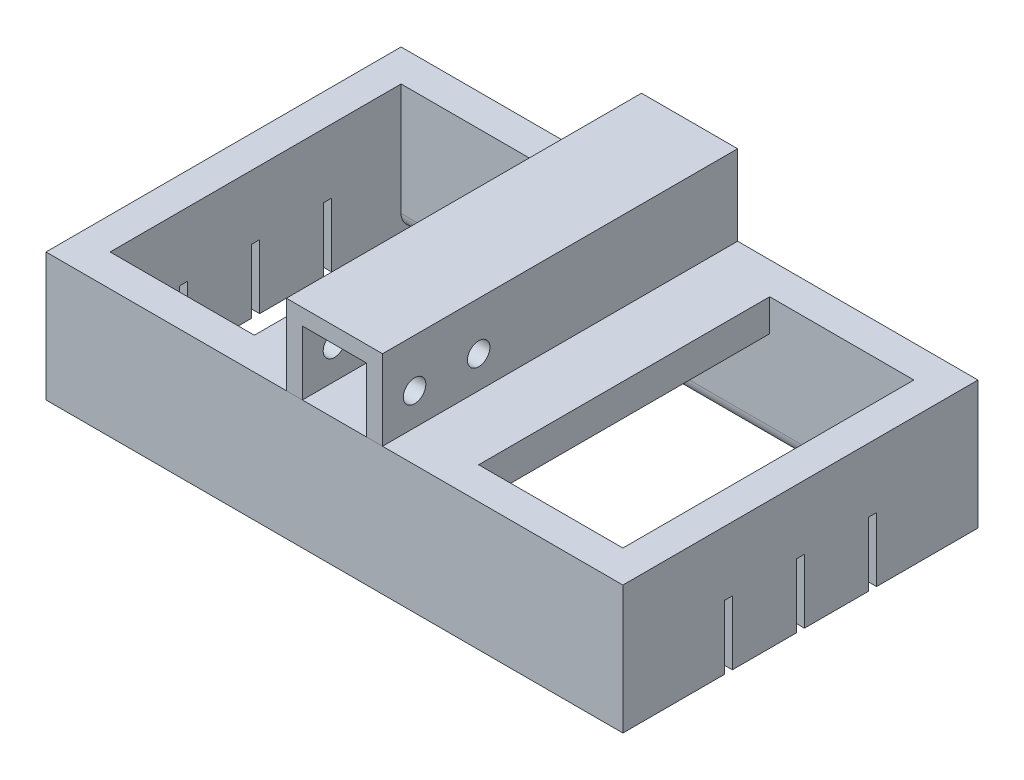
SolidWorks part; units mm, degrees
ref_plane "Front Plane" through (0, 0, 0) normal (0, 0, 1) x (1, 0, 0)
ref_plane "Top Plane" through (0, 0, 0) normal (0, 1, 0) x (1, 0, 0)
ref_plane "Right Plane" through (0, 0, 0) normal (1, 0, 0) x (0, 0, -1)
sketch "Sketch2" plane through (0, 0, 0) normal (0, 1, 0) x (1, 0, 0)
  line L0 (-57.15, -35.179) -> (-57.15, 35.179)
  line L1 (-50.8, -28.829) -> (50.8, -28.829)
  line L2 (-50.8, -28.829) -> (-50.8, 28.829)
  line L3 (-50.8, 28.829) -> (50.8, 28.829)
  line L4 (50.8, -28.829) -> (50.8, 28.829)
  line L5 (-50.8, -28.829) -> (50.8, 28.829) construction
  line L6 (-50.8, 28.829) -> (50.8, -28.829) construction
  line L7 (-57.15, 35.179) -> (57.15, 35.179)
  line L8 (57.15, -35.179) -> (57.15, 35.179)
  line L9 (-57.15, -35.179) -> (57.15, -35.179)
  point P0 (0, 0)
  point P10 (57.15, 35.179)
  dimension "D1" = 57.658
  dimension "D2" = 101.6
  dimension "D3" = 6.35
sketch "Sketch3" plane through (0, 0, 0) normal (0, 0, 1) x (1, 0, 0)
  line L0 (0, 0) -> (0, 12.7) construction
  line L1 (-50.8, 0) -> (50.8, 0) construction
  line L2 (0, 12.7) -> (0, 19.05) construction
  point P6 (0, 0)
  point P8 (0, 0)
  point P11 (0, 0)
  dimension "D1" = 12.7
  dimension "D2" = 6.35
sketch "Sketch4" plane through (0, 0, 0) normal (0, 1, 0) x (1, 0, 0)
  line L4 (-50.8, -28.829) -> (50.8, -28.829)
  line L5 (50.8, -28.829) -> (50.8, 28.829)
  line L6 (50.8, 28.829) -> (-50.8, 28.829)
  line L7 (-50.8, 28.829) -> (-50.8, -28.829)
  line L8 (-50.8, -28.829) -> (50.8, -28.829)
  line L9 (50.8, -28.829) -> (50.8, 28.829)
  line L10 (50.8, 28.829) -> (-50.8, 28.829)
  line L11 (-50.8, 28.829) -> (-50.8, -28.829)
  line L12 (-57.15, 35.179) -> (-57.15, -35.179)
  line L13 (57.15, 35.179) -> (-57.15, 35.179)
  line L14 (57.15, -35.179) -> (57.15, 35.179)
  line L15 (-57.15, -35.179) -> (57.15, -35.179)
  line L16 (-57.15, 35.179) -> (-57.15, -35.179)
  line L17 (57.15, 35.179) -> (-57.15, 35.179)
  line L18 (57.15, -35.179) -> (57.15, 35.179)
  line L19 (-57.15, -35.179) -> (57.15, -35.179)
  dimension "D1" = 0
  dimension "D2" = 0
extrude "Boss-Extrude1" add sketch "Sketch4" along normal up to vertex (19.05 mm away) up to point (0, 19.05, 0)
sketch "Sketch5" plane through (0, 0, 0) normal (0, 1, 0) x (1, 0, 0)
  line L0 (-57.15, -35.179) -> (57.15, -35.179) construction
  line L1 (57.15, -35.179) -> (57.15, 35.179) construction
  line L2 (-57.15, 35.179) -> (57.15, 35.179) construction
  line L3 (-57.15, -35.179) -> (-57.15, 35.179) construction
  line L4 (-57.15, -35.179) -> (57.15, -35.179)
  line L5 (57.15, -35.179) -> (57.15, 35.179)
  line L6 (-57.15, 35.179) -> (57.15, 35.179)
  line L7 (-57.15, -35.179) -> (-57.15, 35.179)
extrude "Boss-Extrude2" add sketch "Sketch5" along normal blind 6.35 from surface contours L4 L5 L6 L7 starting at face at (0, 19.05, 0)
sketch "Sketch6" plane through (-57.15, 0, 0) normal (-1, 0, 0) x (0, 0, 1)
  line L0 (0, 0) -> (0, 12.7)
  line L1 (0, 0) -> (0, 12.7) construction
  line L2 (14.2875, 0) -> (14.2875, 12.7)
  line L3 (35.179, 0) -> (-35.179, 0) construction
  line L4 (-14.2875, 0) -> (-14.2875, 12.7)
  dimension "D1" = 14.2875
  dimension "D2" = 14.2875
extrude "Cut-Extrude-Thin1" cut sketch "Sketch6" against normal through all thin thin type mid plane wall 1.5875
fillet "Fillet1" radius 3.175 2 edges at (0, 0, -28.829) (0, 0, 28.829)
sketch "Sketch8" plane through (0, 0, 35.179) normal (0, 0, 1) x (1, 0, 0)
  line L0 (-9.525, 25.4) -> (-9.525, 41.275)
  line L5 (57.15, 25.4) -> (-57.15, 25.4) construction
  line L6 (-9.525, 41.275) -> (9.525, 41.275)
  line L12 (9.525, 41.275) -> (9.525, 25.4)
  line L13 (9.525, 25.4) -> (6.35, 25.4)
  line L14 (6.35, 25.4) -> (6.35, 38.1)
  line L15 (6.35, 38.1) -> (-6.35, 38.1)
  line L16 (-6.35, 38.1) -> (-6.35, 25.4)
  line L17 (-6.35, 25.4) -> (-9.525, 25.4)
  point P1 (0, 41.275)
  line M7 (57.15, 25.4) -> (-57.15, 25.4)
  dimension "D1" = 12.7
  dimension "D3" = 3.175
  dimension "D2" = 12.7
  dimension "D4" = 3.175
  dimension "D5" = 3.175
extrude "Boss-Extrude3" add sketch "Sketch8" against normal up to surface (70.358 mm away) separate body contours L16 M7 region at (-9.277, 33.3375, 35.179) up to face at (0, 12.7, -35.179)
sketch "Sketch9" plane through (-9.525, 0, 0) normal (-1, 0, 0) x (0, 0, 1)
  line L0 (35.179, 38.1) -> (35.179, 25.4) construction
  line L4 (35.179, 25.4) -> (35.179, 41.275) construction
  circle A0 centre (28.829, 31.75) radius 2.227
  circle A1 centre (16.129, 31.75) radius 2.227
  point P4 (35.179, 31.75)
  point P9 (0, 0)
  point P12 (35.179, 41.275)
  dimension "D2" = 4.454
  dimension "D3" = 12.7
  dimension "D1" = 6.35
extrude "Cut-Extrude2" cut sketch "Sketch9" against normal through all
sketch "Sketch10" plane through (0, 25.4, 0) normal (0, 1, 0) x (1, 0, 0)
  line L0 (-50.8, -28.829) -> (50.8, -28.829) construction
  line L1 (-50.8, 28.829) -> (-22.225, 28.829)
  line L2 (-50.8, 28.829) -> (-50.8, -28.829)
  line L3 (-50.8, -28.829) -> (-22.225, -28.829)
  line L4 (-22.225, 28.829) -> (-22.225, -28.829)
  line L5 (-9.525, 35.179) -> (-9.525, -35.179) construction
  dimension "D1" = 12.7
extrude "Cut-Extrude3" cut sketch "Sketch10" against normal through all
mirror "Mirror1" about plane through (0, 0, 0) normal (1, 0, 0) of "Cut-Extrude3"
equation "\"tightTol\"= 0.005in"
equation "\"normTol\"= 0.01in"
equation "\"looseTol\"= 0.02in"
equation "\"Fry height\"= 0.5in"
equation "\"Fry spacing\"= 0.5625in"
equation "\"Potato width\"= \"Fry spacing\" * 4"
equation "\"Potato length\"= 3.5in"
equation "\"D1@Sketch2\" = \"Potato width\" + \"looseTol\""
equation "\"D2@Sketch2\"=\"Potato length\"+0.5"
equation "\"D1@Sketch3\"=\"Fry height\""
equation "\"D2@Sketch3\"=0.250000in"
equation "\"D1@Sketch6\"=\"Fry spacing\""
equation "\"D2@Sketch6\"=\"Fry spacing\""
equation "\"D2@Sketch9\"=4.2mm+\"normTol\""
